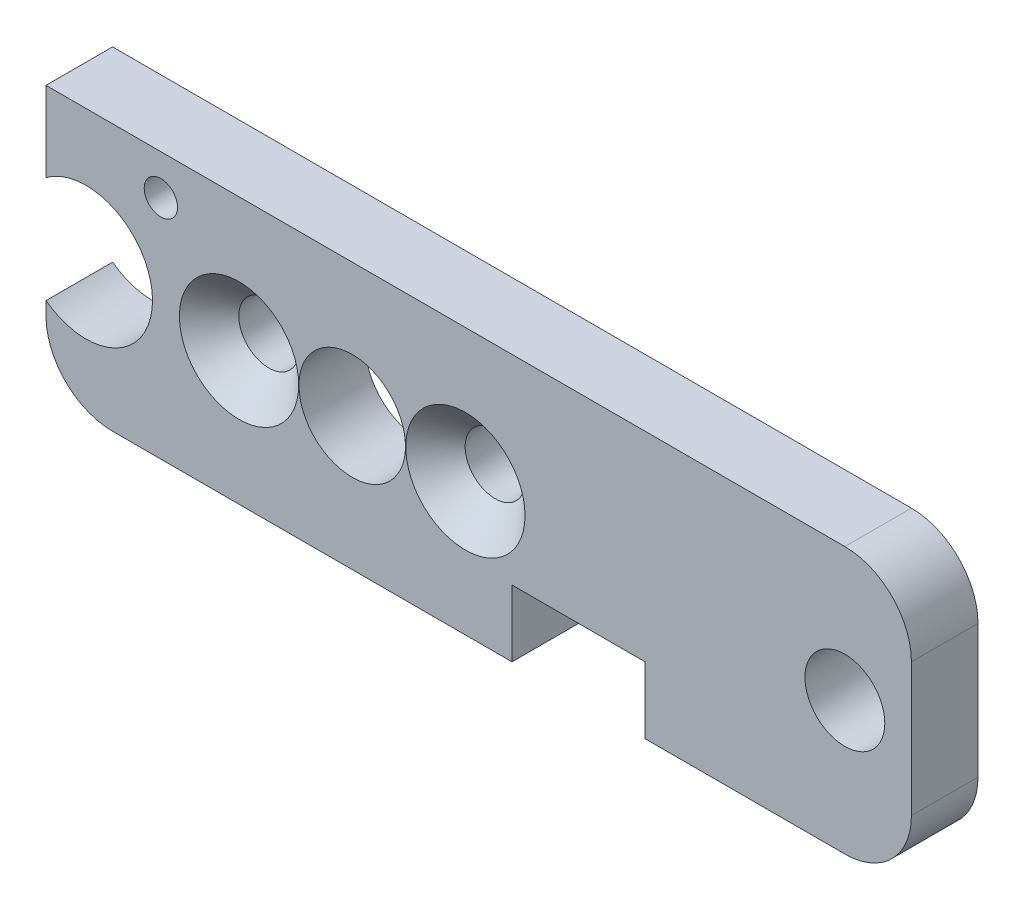
SolidWorks part; units mm, degrees
ref_plane "Front Plane" through (0, 0, 0) normal (0, 0, 1) x (1, 0, 0)
ref_plane "Top Plane" through (0, 0, 0) normal (0, 1, 0) x (1, 0, 0)
ref_plane "Right Plane" through (0, 0, 0) normal (1, 0, 0) x (0, 0, -1)
sketch "Sketch1" plane through (0, 0, 0) normal (0, 0, 1) x (1, 0, 0)
  line L1 (-27.303, 7.4194) -> (37.697, 7.4194)
  line L2 (-27.303, 7.4194) -> (-27.303, -12.5806)
  line L3 (-27.303, -12.5806) -> (37.697, -12.5806)
  line L4 (37.697, 7.4194) -> (37.697, -12.5806)
  dimension "D1" = 65
  dimension "D2" = 20
extrude "Boss-Extrude1" add sketch "Sketch1" along normal blind 5
sketch "Sketch2" plane through (0, 0, 5) normal (0, 0, 1) x (1, 0, 0)
  line L0 (-24.303, -2.5806) -> (-4.303, -2.5806) construction
  line L1 (-27.303, 7.4194) -> (-27.303, -12.5806) construction
  line L2 (-4.303, -2.5806) -> (-10.3134, -8.591) construction
  line L3 (-27.303, -2.5806) -> (-24.303, -2.5806) construction
  line L4 (-4.303, -2.5806) -> (-12.803, -2.5806) construction
  line L5 (-4.303, -2.5806) -> (1.7074, 3.4298) construction
  line L6 (-4.303, -2.5806) -> (4.197, -2.5806) construction
  line L7 (37.697, -2.5806) -> (32.697, -2.5806) construction
  line L8 (37.697, -12.5806) -> (37.697, 7.4194) construction
  dimension "D6" = 8.5
  dimension "D1" = 3
  dimension "D2" = 20
  dimension "D3" = 8.5
  dimension "D4" = 8.5
  dimension "D5" = 8.5
  dimension "D7" = 5
hole_wizard "Ø10.0mm Dowel Hole1" positions "3DSketch2" profile "Sketch4" hole size "Ø10.0" standard "ISO"
sketch3d "3DSketch2"
  point P0 (-24.303, -2.5806, 5)
sketch "Sketch4" plane through (-24.303, -2.5806, 5) normal (1, 0, 0) x (0, -1, 0)
  line L0 (0, 0) -> (0, 28.0043)
  line L1 (0, 28.0043) -> (5, 25)
  line L2 (5, 25) -> (5, 0)
  line L5 (5, 0) -> (0, 0)
  line L10 (0, 28.0043) -> (-5, 25) construction
  line L11 (0, -6.35) -> (0, 107.95) construction
  dimension "Hole Dia." = 10
  dimension "Hole Depth" = 25
  dimension "Drill Angle" = 118
hole_wizard "CSK for M4 Hex Socket Countersunk Cap Screw1" positions "3DSketch5" profile "Sketch8" countersink size "M4" standard "ISO" end condition through all
sketch3d "3DSketch5"
  point P0 (-12.803, -2.5806, 5)
  point P3 (4.197, -2.5806, 5)
sketch "Sketch8" plane through (-12.803, -2.5806, 5) normal (1, 0, 0) x (0, -1, 0)
  line L0 (0, 0) -> (0, 5)
  line L1 (0, 5) -> (2.25, 5)
  line L2 (2.25, 5) -> (2.25, 2.23)
  line L3 (2.25, 2.23) -> (4.48, 0)
  line L5 (4.48, 0) -> (0, 0)
  line L6 (-2.25, 2.23) -> (-4.48, 0) construction
  line L11 (0, -6.35) -> (0, 107.95) construction
  dimension "Thru Hole Dia." = 4.5
  dimension "Thru Hole Depth" = 5
  dimension "Near C'Sink Dia." = 8.96
  dimension "Near C'Sink Angle" = 90
hole_wizard "Ø6.0mm Dowel Hole1" positions "3DSketch6" profile "Sketch9" hole size "Ø6.0" standard "ISO"
sketch3d "3DSketch6"
  point P0 (32.697, -2.5806, 5)
sketch "Sketch9" plane through (32.697, -2.5806, 5) normal (1, 0, 0) x (0, -1, 0)
  line L0 (0, 0) -> (0, 26.8026)
  line L1 (0, 26.8026) -> (3, 25)
  line L2 (3, 25) -> (3, 0)
  line L5 (3, 0) -> (0, 0)
  line L10 (0, 26.8026) -> (-3, 25) construction
  line L11 (0, -6.35) -> (0, 107.95) construction
  dimension "Hole Dia." = 6
  dimension "Hole Depth" = 25
  dimension "Drill Angle" = 118
sketch "Sketch11" plane through (0, 0, 0) normal (0, 0, -1) x (-1, 0, 0)
  line L0 (4.303, -2.5806) -> (4.303, -6.9847) construction
hole_wizard "Ø4.0mm Dowel Hole2" positions "3DSketch8" profile "Sketch13" hole size "Ø4.0" standard "ISO"
sketch3d "3DSketch8"
  point P0 (-4.303, -2.5806, 0)
sketch "Sketch13" plane through (-4.303, -2.5806, 0) normal (1, 0, 0) x (0, 1, 0)
  line L0 (0, 0) -> (0, 26.2017)
  line L1 (0, 26.2017) -> (2, 25)
  line L2 (2, 25) -> (2, 0)
  line L5 (2, 0) -> (0, 0)
  line L10 (0, 26.2017) -> (-2, 25) construction
  line L11 (0, -6.35) -> (0, 107.95) construction
  dimension "Hole Dia." = 4
  dimension "Hole Depth" = 25
  dimension "Drill Angle" = 118
hole_wizard "Ø8.0mm Dowel Hole1" positions "3DSketch9" profile "Sketch14" hole size "Ø8.0" standard "ISO"
sketch3d "3DSketch9"
  point P0 (-4.303, -2.5806, 0)
sketch "Sketch14" plane through (-4.303, -2.5806, 0) normal (1, 0, 0) x (0, 1, 0)
  line L0 (0, 0) -> (0, 7.4034)
  line L1 (0, 7.4034) -> (4, 5)
  line L2 (4, 5) -> (4, 0)
  line L5 (4, 0) -> (0, 0)
  line L10 (0, 7.4034) -> (-4, 5) construction
  line L11 (0, -6.35) -> (0, 107.95) construction
  dimension "Hole Dia." = 8
  dimension "Hole Depth" = 5
  dimension "Drill Angle" = 118
sketch "Sketch22" plane through (0, 0, 0) normal (0, 0, -1) x (-1, 0, 0)
  line L0 (-37.697, -2.5806) -> (-17.697, -2.5806) construction
  line L1 (-17.697, -2.5806) -> (-17.697, -12.5806) construction
  line L2 (27.303, -12.5806) -> (-37.697, -12.5806) construction
  line L3 (-17.697, -12.5806) -> (-17.697, -7.5806)
  line L4 (-17.697, -7.5806) -> (-7.697, -7.5806)
  line L5 (-7.697, -7.5806) -> (-7.697, -12.5806)
  line L6 (-7.697, -12.5806) -> (-17.697, -12.5806)
  dimension "D1" = 20
  dimension "D2" = 5
  dimension "D3" = 10
extrude "Cut-Extrude1" cut sketch "Sketch22" against normal blind 10
sketch "Sketch23" plane through (0, 0, 0) normal (0, 0, -1) x (-1, 0, 0)
  circle A0 centre (4.303, -2.5806) radius 12.5
  circle A1 centre (24.303, -2.5806) radius 5
  dimension "D1" = 25
  dimension "D2" = 10
sketch "Sketch25" plane through (0, -7.5806, 0) normal (0, -1, 0) x (1, 0, 0)
  line L0 (17.697, 2.5) -> (7.697, 2.5) construction
  line L1 (17.697, 5) -> (17.697, 0) construction
  line L2 (7.697, 5) -> (7.697, 0) construction
  line L3 (12.697, 2.5) -> (12.697, 5) construction
  line L4 (17.697, 5) -> (7.697, 5) construction
hole_wizard "M2 Tapped Hole2" positions "3DSketch12" profile "Sketch26" tap size "M2" standard "ISO"
sketch3d "3DSketch12"
  point P0 (12.697, -7.5806, 2.5)
sketch "Sketch26" plane through (12.697, -7.5806, 2.5) normal (1, 0, 0) x (0, 0, -1)
  line L0 (0, 0) -> (0, 7.4807)
  line L1 (0, 7.4807) -> (0.8, 7)
  line L2 (0.8, 7) -> (0.8, 0)
  line L5 (0.8, 0) -> (0, 0)
  line L10 (0, 7.4807) -> (-0.8, 7) construction
  line L11 (0, -6.35) -> (0, 107.95) construction
  dimension "Tap Drill Dia." = 1.6
  dimension "Tap Drill Depth" = 7
  dimension "Drill Angle" = 118
cosmetic thread "Hole Thread1" parameters "D1"=5, "D2"=2
fillet "Fillet1" radius 5 3 edges at (37.697, 7.4194, 2.5) (37.697, -12.5806, 2.5) (-27.303, -12.5806, 2.5)
sketch "Sketch27" plane through (0, 0, 0) normal (0, 0, -1) x (-1, 0, 0)
  line L0 (16.803, -2.5806) -> (16.803, 7.4194) construction
  line L1 (24.303, -2.5806) -> (4.303, -2.5806) construction
  line L2 (-32.697, 7.4194) -> (27.303, 7.4194) construction
  line L3 (27.303, 4.4194) -> (16.803, 4.4194) construction
  line L4 (27.303, 7.4194) -> (27.303, 1.4194) construction
  line L5 (18.6764, 4.4194) -> (18.6764, -2.5806) construction
  circle A0 centre (4.303, -2.5806) radius 12.5 construction
hole_wizard "M3 Tapped Hole2" positions "3DSketch14" profile "Sketch29" tap size "M3" standard "ISO"
sketch3d "3DSketch14"
  point P0 (-18.6764, 4.4194, 0)
sketch "Sketch29" plane through (-18.6764, 4.4194, 0) normal (1, 0, 0) x (0, 1, 0)
  line L0 (0, 0) -> (0, 8.2511)
  line L1 (0, 8.2511) -> (1.25, 7.5)
  line L2 (1.25, 7.5) -> (1.25, 0)
  line L5 (1.25, 0) -> (0, 0)
  line L10 (0, 8.2511) -> (-1.25, 7.5) construction
  line L11 (0, -6.35) -> (0, 107.95) construction
  dimension "Tap Drill Dia." = 2.5
  dimension "Tap Drill Depth" = 7.5
  dimension "Drill Angle" = 118
cosmetic thread "Hole Thread5" parameters "D1"=5, "D2"=3
